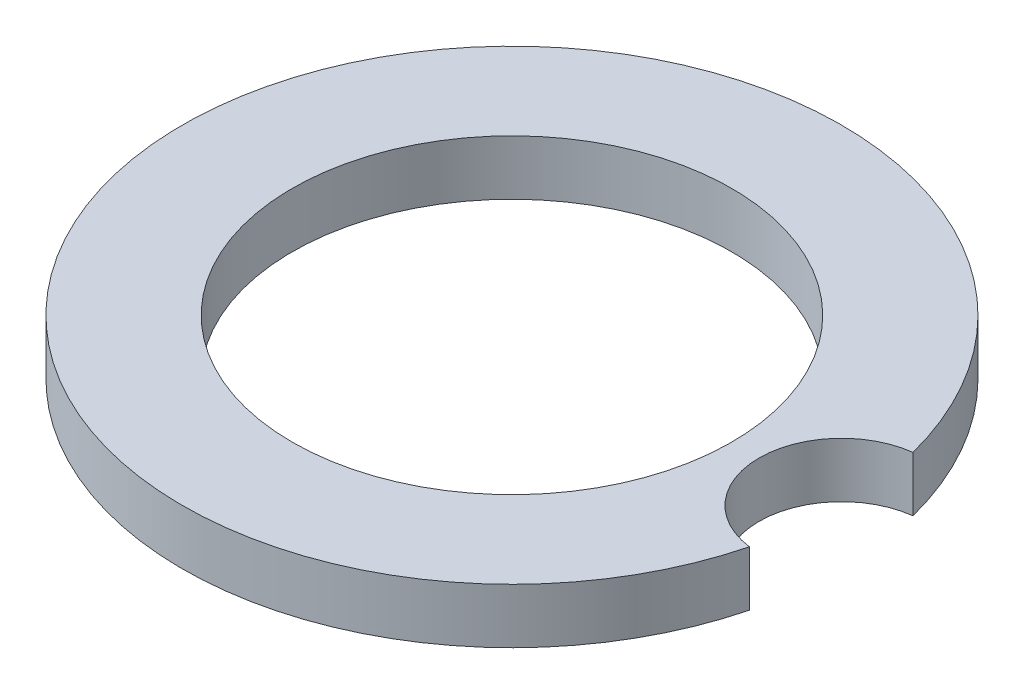
SolidWorks part; units mm, degrees
ref_plane "Front Plane" through (0, 0, 0) normal (0, 0, 1) x (1, 0, 0)
ref_plane "Top Plane" through (0, 0, 0) normal (0, 1, 0) x (1, 0, 0)
ref_plane "Right Plane" through (0, 0, 0) normal (1, 0, 0) x (0, 0, -1)
sketch "Sketch1" plane through (0, 0, 0) normal (0, 1, 0) x (1, 0, 0)
  circle A0 centre (0, 0) radius 50.8
  circle A1 centre (0, 0) radius 76.1746
  dimension "Front_CR_ID" = 101.6
  dimension "Front_CR_OD" = 152.3492
extrude "Boss-Extrude1" add sketch "Sketch1" along normal blind 12.7 contours A1
extrude "Cut-Extrude2" cut sketch "Sketch1<10>" along normal through all contours A0
sketch "Sketch1<10>" plane through (0, 0, 0) normal (0, 1, 0) x (1, 0, 0) same geometry as "Sketch1"
sketch "Sketch2" plane through (0, 12.7, 0) normal (0, 1, 0) x (1, 0, 0)
  line L0 (76.2, 19.05) -> (76.2, -19.05)
  arc A0 (76.2, 19.05) -> (76.2, -19.05) centre (76.1746, 0) ccw
  circle A1 centre (0, 0) radius 76.1746 construction
  dimension "D1" = 38.1
extrude "Cut-Extrude3" cut sketch "Sketch2" against normal through all contours A0 L0
ref_plane "Plane1" through (0, 6.35, 0) normal (0, -1, 0) x (-1, 0, 0)
equation "\"Bodytube_OD\"= 6.17in"
equation "\"Bodytube_ID\"= 5.998in"
equation "\"Motor_OD\"= 4in"
equation "\"Fwd_Tube_Length\"= 38in"
equation "\"Mid_Tube_Length\"= 8in"
equation "\"Aft_Section_Length\"= 40in"
equation "\"Mid_Coupler_Length\"= 13in"
equation "\"Aft_Lower_Length\"= 22in"
equation "\"AB_Coupler_OD_Length\"= 1in"
equation "\"AB_Coupling_Section_Length\"= 0.375in"
equation "\"AB_Coupler_Length\"= \"AB_Coupler_OD_Length\" + \"AB_Coupling_Section_Length\" * 2"
equation "\"Cutout_Angle\"= 80"
equation "\"AB_Paddle_Height\"= 0.375in"
equation "\"AB_Coupler_Num_Screws\"= 6"
equation "\"Num_Cutouts\"= 3"
equation "\"AB_Coupler_OD\"= 6.17in"
equation "\"AB_Coupler_ID\"= 5.75in"
equation "\"AB_Coupler_Surface_Diameter\"= 5.998in"
equation "\"AB_Coupling_Screw_Diameter\"= 0.1065in"
equation "\"AB_Central_Bushing_Length\"= .75in"
equation "\"Lead_Screw_Dist\"= 2.25in"
equation "\"Lead_Screw_Diam\"= (27/64)*1in"
equation "\"Lead_Screw_Length\"= (\"Mid_Coupler_Length\" + 2*0.375in + 2*0.5in)"
equation "\"Paddle_Pin_Offset\"= .25in"
equation "\"Paddle_Pin_Radius\"= 2.25in"
equation "\"Paddle_Gear_OD\"= 3.2in"
equation "\"Fwd_BKHD_From_Top\"= 18in"
equation "\"Front_CR_OD@Sketch1\"=\"Bodytube_ID\""
equation "\"Front_CR_ID@Sketch1\"=\"Motor_OD\""
